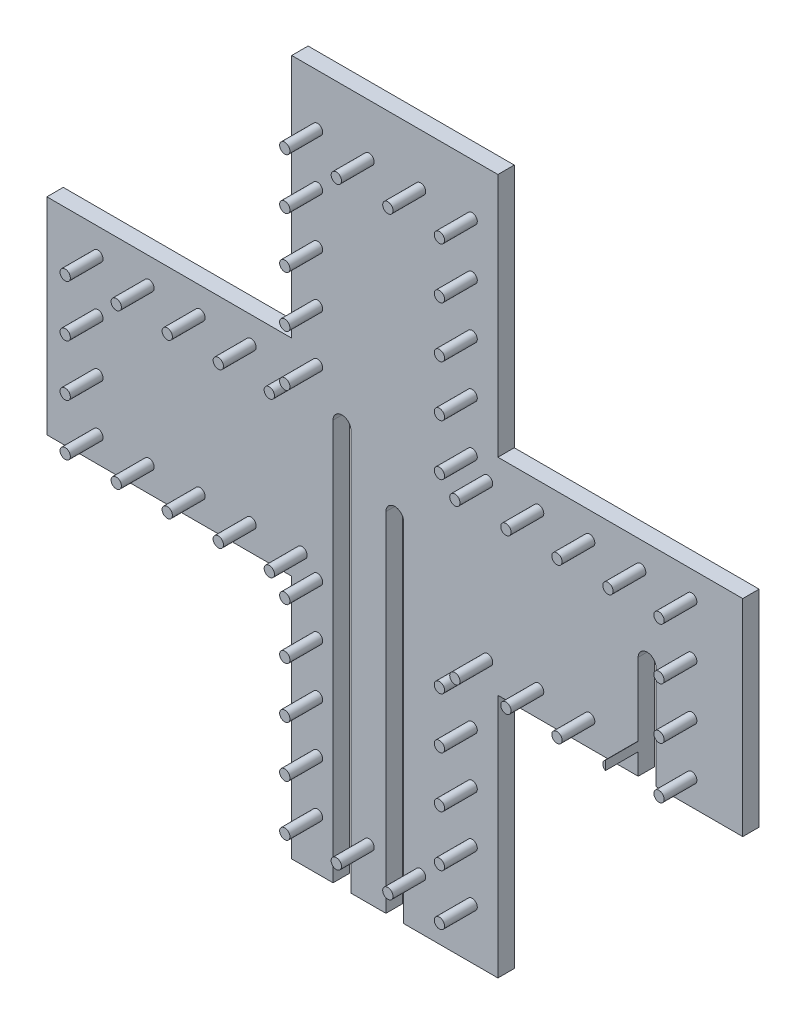
SolidWorks part; units mm, degrees
ref_plane "Front Plane" through (0, 0, 0) normal (0, 0, 1) x (1, 0, 0)
ref_plane "Top Plane" through (0, 0, 0) normal (0, 1, 0) x (1, 0, 0)
ref_plane "Right Plane" through (0, 0, 0) normal (1, 0, 0) x (0, 0, -1)
sketch "Ref" plane through (0, 0, 0) normal (0, 0, 1) x (1, 0, 0)
  line L1 (76.2, -76.2) -> (-76.2, -76.2)
  line L2 (76.2, -76.2) -> (76.2, 76.2)
  line L3 (76.2, 76.2) -> (-76.2, 76.2)
  line L4 (-76.2, -76.2) -> (-76.2, 76.2)
  circle A0 centre (0, 0) radius 2.2479
  circle A1 centre (48.94, 0) radius 2.2479
  circle A2 centre (-10.253, 10.253) radius 2.2479
  circle A3 centre (-10.253, -10.253) radius 2.2479
sketch "Sketch2" plane through (0, 0, 0) normal (0, 0, 1) x (1, 0, 0)
  line L0 (0, 67.5) -> (0, -67.5) construction
  line L1 (20, 67.5) -> (-20, 67.5)
  line L2 (20, 67.5) -> (20, -67.5)
  line L3 (20, -67.5) -> (-20, -67.5)
  line L4 (-20, 67.5) -> (-20, -67.5)
  line L5 (-67.5, 20) -> (67.5, 20)
  line L6 (-67.5, 20) -> (-67.5, -20)
  line L7 (-67.5, -20) -> (67.5, -20)
  line L8 (67.5, 20) -> (67.5, -20)
  line L9 (-67.5, 0) -> (67.5, 0) construction
  line L10 (57.6, 15) -> (47.7, 15) construction
  line L11 (47.7, 15) -> (37.8, 15) construction
  line L12 (37.8, 15) -> (27.9, 15) construction
  line L13 (18, 15) -> (27.9, 15) construction
  line L14 (-15, 57.6) -> (-15, 47.7) construction
  line L15 (-15, 47.7) -> (-15, 37.8) construction
  line L16 (-15, 37.8) -> (-15, 27.9) construction
  line L17 (-15, 27.9) -> (-15, 18) construction
  circle A0 centre (-10.253, 10.253) radius 2.2479
  circle A1 centre (0, 0) radius 2.2479
  circle A2 centre (48.94, 0) radius 2.2479
  circle A3 centre (-10.253, -10.253) radius 2.2479
  circle A4 centre (-10.253, 10.253) radius 2.2479 construction
  circle A6 centre (27.9, 15) radius 1
  circle A7 centre (37.8, 15) radius 1
  circle A8 centre (47.7, 15) radius 1
  circle A9 centre (57.6, 15) radius 1
  circle A10 centre (18, 15) radius 1
  circle A12 centre (57.6, 5) radius 1
  circle A14 centre (27.9, -15) radius 1
  circle A15 centre (37.8, -15) radius 1
  circle A16 centre (47.7, -15) radius 1
  circle A17 centre (57.6, -5) radius 1
  circle A18 centre (57.6, -15) radius 1
  circle A19 centre (18, -15) radius 1
  circle A20 centre (-18, -15) radius 1
  circle A21 centre (-27.9, -15) radius 1
  circle A22 centre (-37.8, -15) radius 1
  circle A23 centre (-47.7, -15) radius 1
  circle A24 centre (-57.6, -15) radius 1
  circle A25 centre (-57.6, -5) radius 1
  circle A26 centre (-57.6, 5) radius 1
  circle A27 centre (-37.8, 15) radius 1
  circle A28 centre (-47.7, 15) radius 1
  circle A29 centre (-57.6, 15) radius 1
  circle A30 centre (-27.9, 15) radius 1
  circle A31 centre (-18, 15) radius 1
  circle A32 centre (-15, 57.6) radius 1
  circle A33 centre (-5, 57.6) radius 1
  circle A34 centre (-15, 47.7) radius 1
  circle A35 centre (-15, 37.8) radius 1
  circle A36 centre (-15, 27.9) radius 1
  circle A37 centre (-15, 18) radius 1
  circle A39 centre (15, 18) radius 1
  circle A40 centre (15, 27.9) radius 1
  circle A41 centre (15, 37.8) radius 1
  circle A42 centre (15, 47.7) radius 1
  circle A43 centre (15, 57.6) radius 1
  circle A44 centre (5, 57.6) radius 1
  circle A45 centre (-15, -18) radius 1
  circle A46 centre (-15, -27.9) radius 1
  circle A47 centre (-15, -37.8) radius 1
  circle A48 centre (-15, -47.7) radius 1
  circle A49 centre (-15, -57.6) radius 1
  circle A50 centre (-5, -57.6) radius 1
  circle A51 centre (5, -57.6) radius 1
  circle A52 centre (15, -57.6) radius 1
  circle A53 centre (15, -47.7) radius 1
  circle A54 centre (15, -37.8) radius 1
  circle A55 centre (15, -27.9) radius 1
  circle A56 centre (15, -18) radius 1
  circle A57 centre (-10.253, 10.253) radius 1.725
  circle A58 centre (0, 0) radius 1.725
  circle A59 centre (-10.253, -10.253) radius 1.725
  circle A60 centre (48.94, 0) radius 1.725
  point P23 (67.5, 0)
  point P24 (0, 67.5)
  point P26 (-20, 0)
  point P28 (0, -20)
  dimension "D7" = 2
  dimension "D11" = 2
  dimension "D14" = 3.45
  dimension "D1" = 40
  dimension "D2" = 135
  dimension "D3" = 135
  dimension "D4" = 9.9
  dimension "D5" = 9.9
  dimension "D6" = 5
  dimension "D8" = 47.5
  dimension "D9" = 10
  dimension "D10" = 10
  dimension "D12" = 9.9
  dimension "D13" = 5
extrude "Boss-Extrude1" add sketch "Sketch2" along normal blind 3.175 contours L4 L5 L2 L1 A43 A41 A32 A33 A34 A35 A36 A40 A42 A44 | L8 L5 L2 L7 A17 A15 A2 A6 A7 A8 A9 A12 A14 A16 A18 | L4 L7 L2 L5 A56 A39 A37 A19 A10 A3 A1 A0 A20 A31 A45 | L6 L7 L4 L5 A29 A27 A21 A22 A23 A24 A25 A26 A28 A30 | L7 L4 L3 L2 A55 A54 A53 A52 A51 A49 A47 A46 A48 A50 | A32 | A33 | A44 | A43 | A42 | A34 | A41 | A40 | A36 | A35 | A31 | A37 | A30 | A27 | A28 | A29 | A26 | A25 | A24 | A23 | A20 | A45 | A22 | A46 | A47 | A48 | A49 | A50 | A51 | A52 | A53 | A54 | A56 | A19 | A55 | A14 | A15 | A18 | A17 | A16 | A8 | A9 | A12 | A39 | A10 | A7 | A6 | A0 | A1 | A3 | A2 | A21 region at (0, 43.7169, 0) region at (43.6721, 0, 0) region at (19.4343, 0, 0) region at (-43.7169, 0, 0) region at (0, -43.7169, 0) region at (-12.4374, 10.253, 0) region at (-2.1843, 0, 0) region at (46.7557, 0, 0) region at (-12.4374, -10.253, 0) region at (27.9, 15, 0) region at (37.8, 15, 0) region at (47.7, 15, 0) region at (57.6, 15, 0) region at (18, 15, 0) region at (57.6, 5, 0) region at (27.9, -15, 0) region at (37.8, -15, 0) region at (47.7, -15, 0) region at (57.6, -5, 0) region at (57.6, -15, 0) region at (18, -15, 0) region at (-18, -15, 0) region at (-37.8, -15, 0) region at (-47.7, -15, 0) region at (-57.6, -15, 0) region at (-57.6, -5, 0) region at (-57.6, 5, 0) region at (-37.8, 15, 0) region at (-47.7, 15, 0) region at (-57.6, 15, 0) region at (-27.9, 15, 0) region at (-18, 15, 0) region at (-15, 57.6, 0) region at (-5, 57.6, 0) region at (-15, 47.7, 0) region at (-15, 37.8, 0) region at (-15, 27.9, 0) region at (-15, 18, 0) region at (15, 18, 0) region at (15, 27.9, 0) region at (15, 37.8, 0) region at (15, 47.7, 0) region at (15, 57.6, 0) region at (5, 57.6, 0) region at (-15, -18, 0) region at (-15, -27.9, 0) region at (-15, -37.8, 0) region at (-15, -47.7, 0) region at (-15, -57.6, 0) region at (-5, -57.6, 0) region at (5, -57.6, 0) region at (15, -57.6, 0) region at (15, -47.7, 0) region at (15, -37.8, 0) region at (15, -27.9, 0) region at (15, -18, 0)
extrude "Boss-Extrude2" add sketch "Sketch2<3>" along normal blind 6.35 from surface contours A52 | A51 | A50 | A49 | A48 | A47 | A54 | A53 | A46 | A55 | A45 | A20 | A21 | A22 | A23 | A24 | A25 | A26 | A29 | A28 | A30 | A31 | A37 | A36 | A35 | A34 | A32 | A33 | A44 | A43 | A42 | A40 | A41 | A39 | A10 | A6 | A7 | A8 | A9 | A12 | A17 | A18 | A16 | A15 | A56 | A19 | A14 | A27 region at (27.9, 15, 0) region at (37.8, 15, 0) region at (47.7, 15, 0) region at (57.6, 15, 0) region at (18, 15, 0) region at (57.6, 5, 0) region at (27.9, -15, 0) region at (37.8, -15, 0) region at (47.7, -15, 0) region at (57.6, -5, 0) region at (57.6, -15, 0) region at (18, -15, 0) region at (-18, -15, 0) region at (-27.9, -15, 0) region at (-37.8, -15, 0) region at (-47.7, -15, 0) region at (-57.6, -15, 0) region at (-57.6, -5, 0) region at (-57.6, 5, 0) region at (-47.7, 15, 0) region at (-57.6, 15, 0) region at (-27.9, 15, 0) region at (-18, 15, 0) region at (-15, 57.6, 0) region at (-5, 57.6, 0) region at (-15, 47.7, 0) region at (-15, 37.8, 0) region at (-15, 27.9, 0) region at (-15, 18, 0) region at (15, 18, 0) region at (15, 27.9, 0) region at (15, 37.8, 0) region at (15, 47.7, 0) region at (15, 57.6, 0) region at (5, 57.6, 0) region at (-15, -18, 0) region at (-15, -27.9, 0) region at (-15, -37.8, 0) region at (-15, -47.7, 0) region at (-15, -57.6, 0) region at (-5, -57.6, 0) region at (5, -57.6, 0) region at (15, -57.6, 0) region at (15, -47.7, 0) region at (15, -37.8, 0) region at (15, -27.9, 0) region at (15, -18, 0) starting at face at (0, 0, 3.175)
sketch "Sketch2<3>" plane through (0, 0, 0) normal (0, 0, 1) x (1, 0, 0) same geometry as "Sketch2"
sketch "Sketch3" plane through (0, 0, 0) normal (0, 0, 1) x (1, 0, 0)
  line L0 (-10.253, 10.253) -> (-10.253, -86.7198) construction
  line L1 (-8.528, 10.253) -> (-8.528, -86.7198)
  line L2 (-11.978, 10.253) -> (-11.978, -86.7198)
  line L3 (0, 0) -> (0, -86.7102) construction
  line L4 (1.725, 0) -> (1.725, -86.7102)
  line L5 (-1.725, 0) -> (-1.725, -86.7102)
  line L6 (48.94, 0) -> (48.94, -52.394) construction
  line L7 (50.665, 0) -> (50.665, -52.394)
  line L8 (47.215, 0) -> (47.215, -52.394)
  arc A0 (-8.528, 10.253) -> (-11.978, 10.253) centre (-10.253, 10.253) ccw
  arc A1 (-11.978, -86.7198) -> (-8.528, -86.7198) centre (-10.253, -86.7198) ccw
  arc A2 (1.725, 0) -> (-1.725, 0) centre (0, 0) ccw
  arc A3 (-1.725, -86.7102) -> (1.725, -86.7102) centre (0, -86.7102) ccw
  arc A4 (50.665, 0) -> (47.215, 0) centre (48.94, 0) ccw
  arc A5 (47.215, -52.394) -> (50.665, -52.394) centre (48.94, -52.394) ccw
  point P3 (-10.253, -38.2334)
  point P8 (0, -43.3551)
  point P16 (48.94, -26.197)
  dimension "D1" = 1.725
extrude "Cut-Extrude3" cut sketch "Sketch3" along normal through all both contours L8 A5 L7 A4 | L5 A3 L4 A2 | L2 A1 L1 A0 region at (-10.253, -38.2334, 0) region at (0, -43.3551, 0) region at (48.94, -26.197, 0)
equation "\"D12@Sketch2\"=\"D4@Sketch2\""
equation "\"D13@Sketch2\"=\"D6@Sketch2\""
